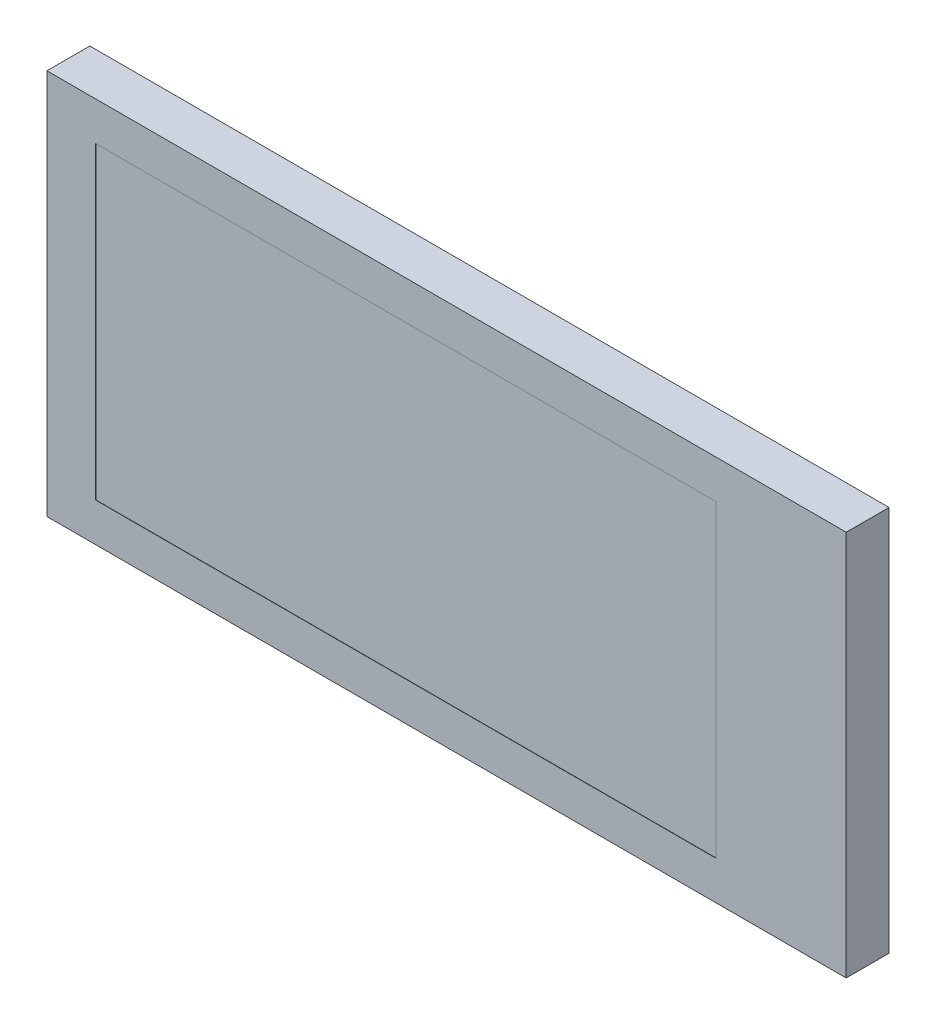
SolidWorks part; units mm, degrees
ref_plane "前视基准面" through (0, 0, 0) normal (0, 0, 1) x (1, 0, 0)
ref_plane "上视基准面" through (0, 0, 0) normal (0, 1, 0) x (1, 0, 0)
ref_plane "右视基准面" through (0, 0, 0) normal (1, 0, 0) x (0, 0, -1)
sketch "草图1" plane through (0, 0, 0) normal (0, 0, 1) x (1, 0, 0)
  line L1 (0, 0) -> (27.95, 0)
  line L2 (0, 0) -> (0, 13.5)
  line L3 (0, 13.5) -> (27.95, 13.5)
  line L4 (27.95, 0) -> (27.95, 13.5)
  line L5 (1.7, 1.35) -> (23.4, 1.35)
  line L6 (1.7, 1.35) -> (1.7, 12.15)
  line L7 (1.7, 12.15) -> (23.4, 12.15)
  line L8 (23.4, 1.35) -> (23.4, 12.15)
  dimension "D1" = 27.95
  dimension "D2" = 13.5
  dimension "D3" = 1.7
  dimension "D4" = 1.35
  dimension "D5" = 21.7
  dimension "D6" = 10.8
extrude "凸台-拉伸1" add sketch "草图1" along normal blind 1.5
extrude "凸台-拉伸2" add sketch "草图1<2>" along normal blind 1.49 contours L5 L8 L7 L6 region at (12.55, 6.75, 0)
sketch "草图1<2>" plane through (0, 0, 0) normal (0, 0, 1) x (1, 0, 0) same geometry as "草图1"
